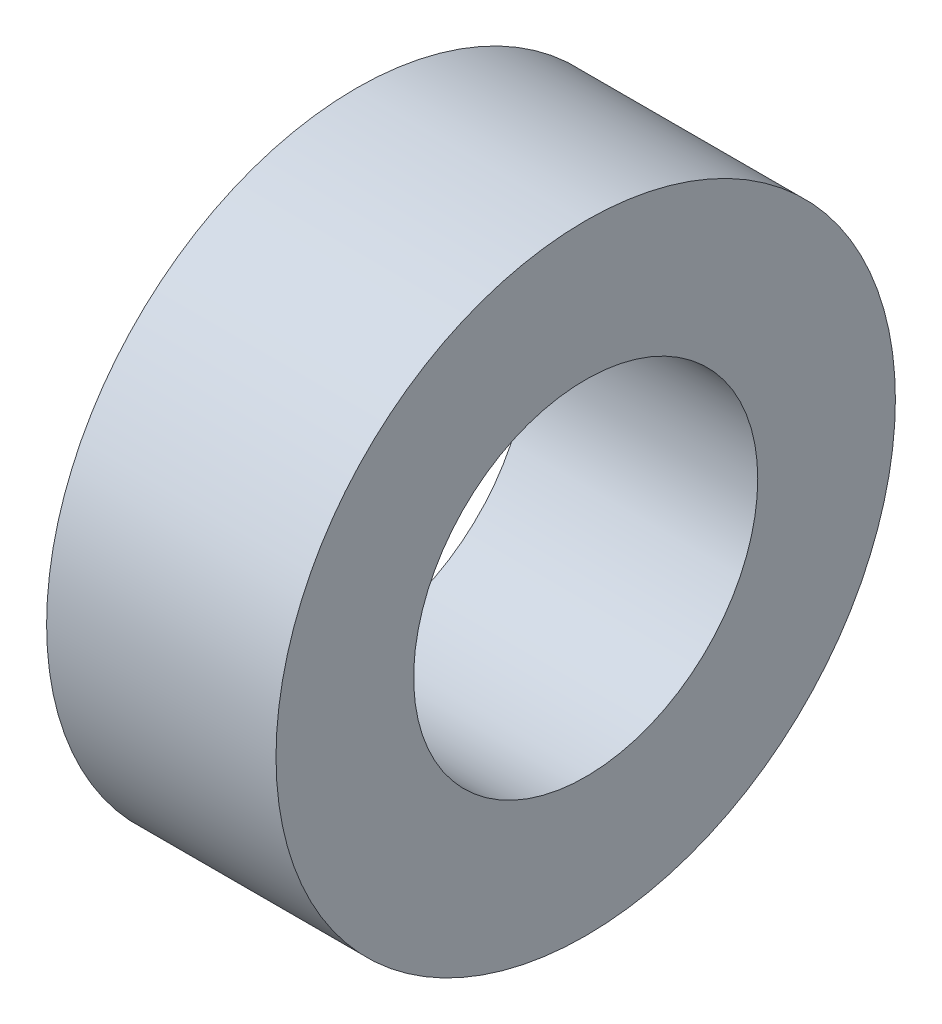
SolidWorks part; units mm, degrees
ref_plane "Ebene vorne" through (0, 0, 0) normal (1, 0, 0) x (0, 1, 0)
ref_plane "Ebene oben" through (0, 0, 0) normal (0, 0, 1) x (0, 1, 0)
ref_plane "Ebene rechts" through (0, 0, 0) normal (0, 1, 0) x (-1, 0, 0)
sketch "Skizze1" plane through (0, 0, 0) normal (1, 0, 0) x (0, 1, 0)
  circle A0 centre (0, 0) radius 6.75
extrude "Aufsatz-Linear austragen1" add sketch "Skizze1" along normal blind 5 contours A0
sketch "Skizze2" plane through (0, 0, 0) normal (1, 0, 0) x (0, 1, 0)
  circle A1 centre (0, 0) radius 3.75
extrude "Schnitt-Linear austragen1" cut sketch "Skizze2" along normal blind 5
